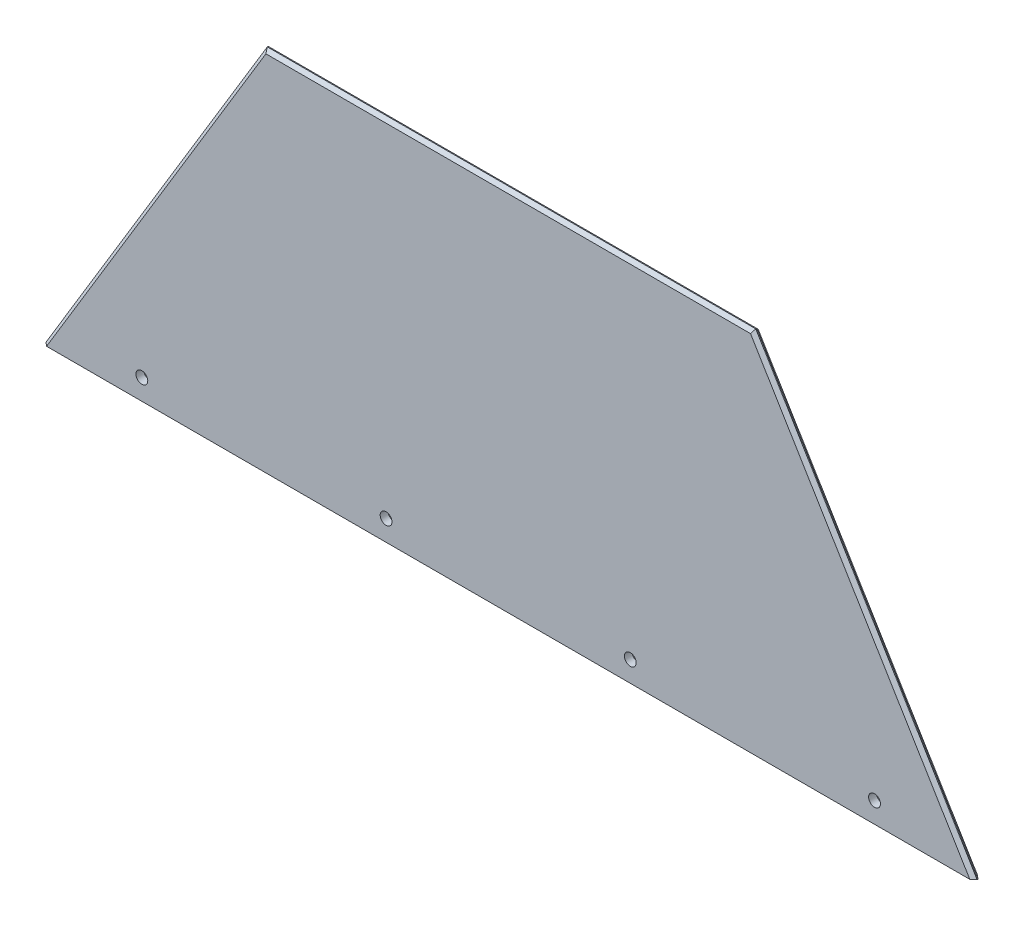
SolidWorks part; units mm, degrees
material "Printed Circuit Board"
ref_plane "Front Plane" through (0, 0, 0) normal (0, 0, 1) x (1, 0, 0)
ref_plane "Top Plane" through (0, 0, 0) normal (0, 1, 0) x (1, 0, 0)
ref_plane "Right Plane" through (0, 0, 0) normal (1, 0, 0) x (0, 0, -1)
sketch "Sketch1" plane through (0, 0, 0) normal (0, 0, 1) x (1, 0, 0)
  line L0 (0, 0) -> (193.675, 0)
  line L1 (193.675, 0) -> (101.6, 152.4)
  line L2 (101.6, 152.4) -> (0, 152.4)
  line L3 (0, 152.4) -> (-101.6, 152.4)
  line L4 (-101.6, 152.4) -> (-193.675, 0)
  line L5 (-193.675, 0) -> (0, 0)
  line L6 (0, 0) -> (0, 152.4) construction
  dimension "D1" = 152.4
  dimension "D2" = 387.35
  dimension "D3" = 203.2
extrude "Extrude1" add sketch "Sketch1" along normal mid plane 3.175
ref_plane "Plane1" through (0, 0, 0) normal (-1, 0, 0) x (0, 0, 1)
chamfer "Chamfer1" distance 1.397 angle 45 6 edges at (147.6375, 76.2, -1.5875) (0, 152.4, -1.5875) (-147.6375, 76.2, -1.5875) (147.6375, 76.2, 1.5875) (0, 152.4, 1.5875) (-147.6375, 76.2, 1.5875)
sketch "Sketch2" plane through (0, 0, 1.5875) normal (0, 0, 1) x (1, 0, 0)
  line L0 (193.675, 0) -> (50.8, 0) construction
  line L1 (-192.0428, 0) -> (192.0428, 0) construction
  line L2 (50.8, 0) -> (50.8, 8.5852) construction
  line L3 (0, 1.7463) -> (0, -1.7463) construction
  dimension "D1" = 50.8
  dimension "D2" = 8.5852
hole_wizard "#10 (0.1935) Diameter Hole1" positions "3DSketch1" profile "Sketch4" hole size "#10" standard "Ansi Inch" end condition through all
sketch3d "3DSketch1"
  point P0 (50.8, 8.5852, 1.5875)
sketch "Sketch4" plane through (50.8, 8.5852, 1.5875) normal (1, 0, 0) x (0, -1, 0)
  line L0 (0, 0) -> (0, 3.175)
  line L1 (0, 3.175) -> (2.4574, 3.175)
  line L2 (2.4574, 3.175) -> (2.4574, 0)
  line L5 (2.4574, 0) -> (0, 0)
  line L11 (0, -6.35) -> (0, 107.95) construction
  dimension "Thru Hole Dia." = 4.9149
  dimension "Thru Hole Depth" = 3.175
pattern_linear "LPattern2" count 3 spacing 101.6 along (-1, 0, 0) count 2 spacing 101.6 along (1, 0, 0) of "#10 (0.1935) Diameter Hole1"
